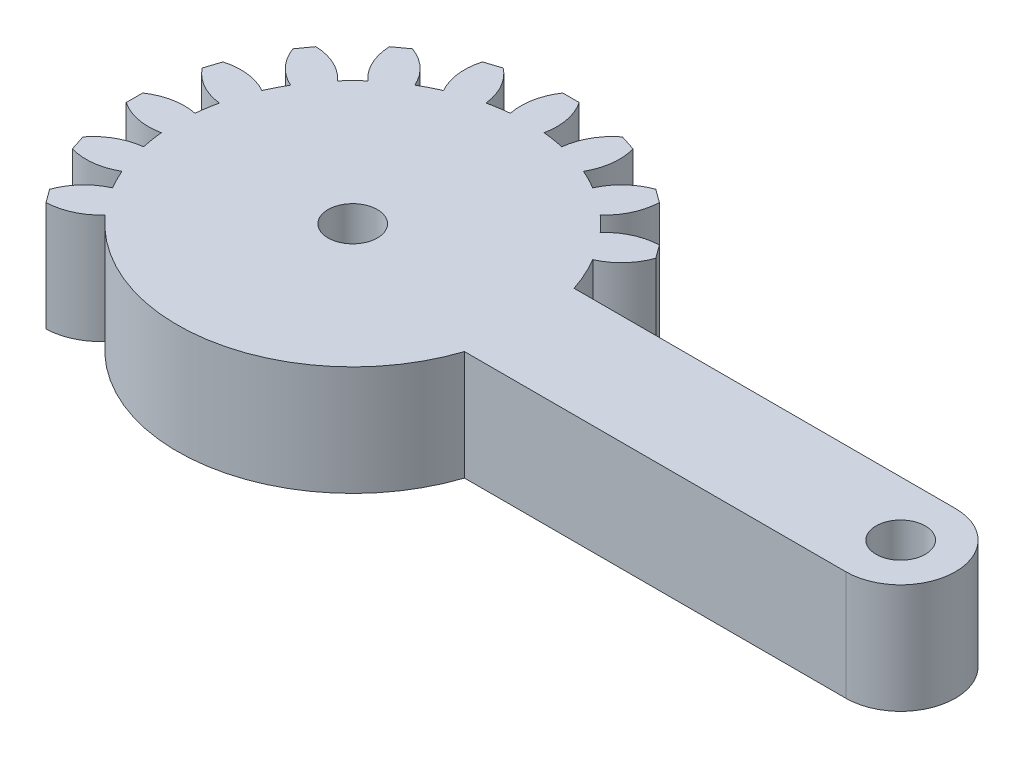
SolidWorks part; units mm, degrees
ref_plane "Front Plane" through (0, 0, 0) normal (0, 0, 1) x (1, 0, 0)
ref_plane "Top Plane" through (0, 0, 0) normal (0, 1, 0) x (1, 0, 0)
ref_plane "Right Plane" through (0, 0, 0) normal (1, 0, 0) x (0, 0, -1)
sketch "Sketch2" plane through (0, 0, 0) normal (0, 1, 0) x (1, 0, 0)
  line L0 (0, 0) -> (50, 0) construction
  line L1 (0, 16) -> (0, -16) construction
  line L3 (50, 5) -> (50, -5) construction
  line L4 (50, 5) -> (15.1987, 5)
  line L5 (50, -5) -> (15.1987, -5)
  line L19 (0, 16) -> (0, 19.9175) construction
  line L23 (0.75, 19.9175) -> (-0.75, 19.9175)
  line L24 (6.8681, 18.7109) -> (5.4416, 19.1744)
  line L25 (12.314, 15.6728) -> (11.1005, 16.5544)
  line L26 (16.5544, 11.1005) -> (15.6728, 12.314)
  line L27 (19.1744, 5.4416) -> (18.7109, 6.8681)
  line L28 (19.9175, -0.75) -> (19.9175, 0.75)
  line L29 (18.7109, -6.8681) -> (19.1744, -5.4416)
  line L30 (15.6728, -12.314) -> (16.5544, -11.1005)
  line L31 (11.1005, -16.5544) -> (12.314, -15.6728)
  line L32 (5.4416, -19.1744) -> (6.8681, -18.7109)
  line L33 (-0.75, -19.9175) -> (0.75, -19.9175)
  line L34 (-6.8681, -18.7109) -> (-5.4416, -19.1744)
  line L35 (-12.314, -15.6728) -> (-11.1005, -16.5544)
  line L36 (-16.5544, -11.1005) -> (-15.6728, -12.314)
  line L37 (-19.1744, -5.4416) -> (-18.7109, -6.8681)
  line L38 (-19.9175, 0.75) -> (-19.9175, -0.75)
  line L39 (-18.7109, 6.8681) -> (-19.1744, 5.4416)
  line L40 (-15.6728, 12.314) -> (-16.5544, 11.1005)
  line L41 (-11.1005, 16.5544) -> (-12.314, 15.6728)
  line L42 (-5.4416, 19.1744) -> (-6.8681, 18.7109)
  circle A1 centre (50, 0) radius 2.25
  arc A4 (50, 5) -> (50, -5) centre (50, 0) cw
  circle A5 centre (0, 0) radius 16
  arc A47 (-0.75, 19.9175) -> (-1.5376, 15.9259) centre (3.5663, 16.9924) ccw
  arc A48 (0.75, 19.9175) -> (1.5376, 15.9259) centre (-3.5663, 16.9924) cw
  arc A49 (5.4416, 19.1744) -> (3.4591, 15.6216) centre (8.6427, 15.0586) ccw
  arc A50 (6.8681, 18.7109) -> (6.3837, 14.6713) centre (1.8591, 17.2628) cw
  arc A51 (11.1005, 16.5544) -> (8.1171, 13.7881) centre (12.8731, 11.6509) ccw
  arc A52 (12.314, 15.6728) -> (10.605, 11.9806) centre (7.1026, 15.8434) cw
  arc A53 (15.6728, 12.314) -> (11.9806, 10.605) centre (15.8434, 7.1026) ccw
  arc A54 (16.5544, 11.1005) -> (13.7881, 8.1171) centre (11.6509, 12.8731) cw
  arc A55 (18.7109, 6.8681) -> (14.6713, 6.3837) centre (17.2628, 1.8591) ccw
  arc A56 (19.1744, 5.4416) -> (15.6216, 3.4591) centre (15.0586, 8.6427) cw
  arc A57 (19.9175, 0.75) -> (15.9259, 1.5376) centre (16.9924, -3.5663) ccw
  arc A58 (19.9175, -0.75) -> (15.9259, -1.5376) centre (16.9924, 3.5663) cw
  arc A59 (19.1744, -5.4416) -> (15.6216, -3.4591) centre (15.0586, -8.6427) ccw
  arc A60 (18.7109, -6.8681) -> (14.6713, -6.3837) centre (17.2628, -1.8591) cw
  arc A61 (16.5544, -11.1005) -> (13.7881, -8.1171) centre (11.6509, -12.8731) ccw
  arc A62 (15.6728, -12.314) -> (11.9806, -10.605) centre (15.8434, -7.1026) cw
  arc A63 (12.314, -15.6728) -> (10.605, -11.9806) centre (7.1026, -15.8434) ccw
  arc A64 (11.1005, -16.5544) -> (8.1171, -13.7881) centre (12.8731, -11.6509) cw
  arc A65 (6.8681, -18.7109) -> (6.3837, -14.6713) centre (1.8591, -17.2628) ccw
  arc A66 (5.4416, -19.1744) -> (3.4591, -15.6216) centre (8.6427, -15.0586) cw
  arc A67 (0.75, -19.9175) -> (1.5376, -15.9259) centre (-3.5663, -16.9924) ccw
  arc A68 (-0.75, -19.9175) -> (-1.5376, -15.9259) centre (3.5663, -16.9924) cw
  arc A69 (-5.4416, -19.1744) -> (-3.4591, -15.6216) centre (-8.6427, -15.0586) ccw
  arc A70 (-6.8681, -18.7109) -> (-6.3837, -14.6713) centre (-1.8591, -17.2628) cw
  arc A71 (-11.1005, -16.5544) -> (-8.1171, -13.7881) centre (-12.8731, -11.6509) ccw
  arc A72 (-12.314, -15.6728) -> (-10.605, -11.9806) centre (-7.1026, -15.8434) cw
  arc A73 (-15.6728, -12.314) -> (-11.9806, -10.605) centre (-15.8434, -7.1026) ccw
  arc A74 (-16.5544, -11.1005) -> (-13.7881, -8.1171) centre (-11.6509, -12.8731) cw
  arc A75 (-18.7109, -6.8681) -> (-14.6713, -6.3837) centre (-17.2628, -1.8591) ccw
  arc A76 (-19.1744, -5.4416) -> (-15.6216, -3.4591) centre (-15.0586, -8.6427) cw
  arc A77 (-19.9175, -0.75) -> (-15.9259, -1.5376) centre (-16.9924, 3.5663) ccw
  arc A78 (-19.9175, 0.75) -> (-15.9259, 1.5376) centre (-16.9924, -3.5663) cw
  arc A79 (-19.1744, 5.4416) -> (-15.6216, 3.4591) centre (-15.0586, 8.6427) ccw
  arc A80 (-18.7109, 6.8681) -> (-14.6713, 6.3837) centre (-17.2628, 1.8591) cw
  arc A81 (-16.5544, 11.1005) -> (-13.7881, 8.1171) centre (-11.6509, 12.8731) ccw
  arc A82 (-15.6728, 12.314) -> (-11.9806, 10.605) centre (-15.8434, 7.1026) cw
  arc A83 (-12.314, 15.6728) -> (-10.605, 11.9806) centre (-7.1026, 15.8434) ccw
  arc A84 (-11.1005, 16.5544) -> (-8.1171, 13.7881) centre (-12.8731, 11.6509) cw
  arc A85 (-6.8681, 18.7109) -> (-6.3837, 14.6713) centre (-1.8591, 17.2628) ccw
  arc A86 (-5.4416, 19.1744) -> (-3.4591, 15.6216) centre (-8.6427, 15.0586) cw
  circle A87 centre (0, 0) radius 2.25
  point P7 (0, 0)
  point P18 (50, 0)
  point P137 (0, 0)
  point P162 (0, 0)
  dimension "D1" = 32
  dimension "D3" = 4.5
  dimension "D4" = 1.5
  dimension "D7" = 4.5
  dimension "D2" = 50
  dimension "D5" = 20
  dimension "D6" = 10
extrude "Boss-Extrude1" add sketch "Sketch2" along normal blind 10 contours A59 L5 A4 L4 A56 A5 A57 L28 A58 A1 | A54 L26 A53 A5 | A52 L25 A51 A5 | A50 L24 A49 A5 | A48 L23 A47 A5 | A86 L42 A85 A5 | A84 L41 A83 A5 | A82 L40 A81 A5 | A80 L39 A79 A5 | A78 L38 A77 A5 | A76 L37 A75 A5 | A74 L36 A73 A5 | L5 A59 A5 | A58 L28 A57 A5 | A56 L4 A5 | A5 A87
